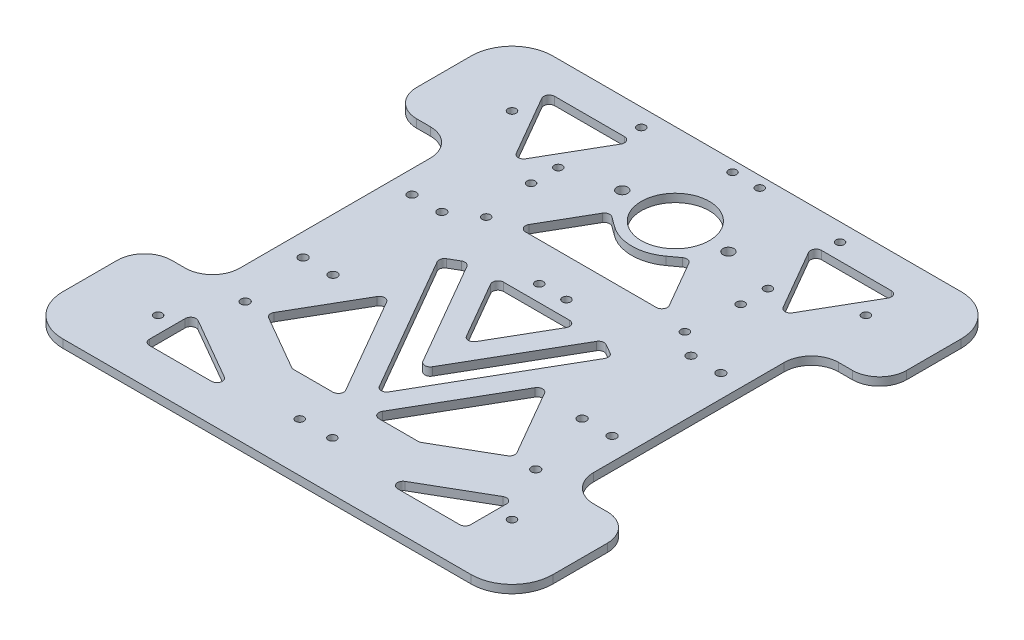
SolidWorks part; units mm, degrees
material "ABS"
ref_plane "Спереди" through (0, 0, 0) normal (0, 0, 1) x (1, 0, 0)
ref_plane "Сверху" through (0, 0, 0) normal (0, 1, 0) x (1, 0, 0)
ref_plane "Справа" through (0, 0, 0) normal (1, 0, 0) x (0, 0, -1)
sketch "Sketch1" plane through (0, 0, 0) normal (0, 1, 0) x (1, 0, 0)
  line L1 (-90, 90) -> (90, 90)
  line L2 (-90, 90) -> (-90, -90)
  line L3 (-90, -90) -> (90, -90)
  line L4 (90, 90) -> (90, -90)
  line L5 (-90, 90) -> (90, -90) construction
  line L6 (-90, -90) -> (90, 90) construction
  point P0 (0, 0)
  dimension "D1" = 180
  dimension "D2" = 180
extrude "Boss-Extrude1" add sketch "Sketch1" along normal blind 3
fillet "Fillet1" radius 15 4 edges at (-90, 1.5, -90) (90, 1.5, -90) (-90, 1.5, 90) (90, 1.5, 90)
sketch "Sketch2" plane through (0, 3, 0) normal (0, 1, 0) x (1, 0, 0)
  line L0 (0, 0) -> (-77.5, 0) construction
  line L1 (2.75, 0) -> (-2.75, 0) construction
  line L2 (-90, 75) -> (-90, -75) construction
  line L3 (-90, 45) -> (-65, 45)
  line L4 (-90, 45) -> (-90, -45)
  line L5 (-90, -45) -> (-65, -45)
  line L6 (-65, 45) -> (-65, -45)
  line L7 (-90, 45) -> (-65, -45) construction
  line L8 (-90, -45) -> (-65, 45) construction
  line L9 (0, 0) -> (0, 45) construction
  line L10 (90, -45) -> (65, 45) construction
  line L11 (90, 45) -> (65, -45) construction
  line L12 (65, 45) -> (65, -45)
  line L13 (90, -45) -> (65, -45)
  line L14 (90, 45) -> (90, -45)
  line L15 (90, 45) -> (65, 45)
  circle A0 centre (-56.75, 20) radius 1.6
  circle A1 centre (-45.75, 20) radius 1.6
  circle A2 centre (-56.75, -20) radius 1.6
  circle A3 centre (-45.75, -20) radius 1.6
  circle A4 centre (45.75, 20) radius 1.6
  circle A5 centre (56.75, 20) radius 1.6
  circle A6 centre (45.75, -20) radius 1.6
  circle A7 centre (56.75, -20) radius 1.6
  dimension "D1" = 25
  dimension "D2" = 90
extrude "Cut-Extrude2" cut sketch "Sketch2" against normal through all
fillet "Fillet2" radius 10 8 edges at (-65, 1.5, 45) (-65, 1.5, -45) (65, 1.5, -45) (65, 1.5, 45) (90, 1.5, -45) (90, 1.5, 45) (-90, 1.5, 45) (-90, 1.5, -45)
hole_wizard "Диаметр отверстия Ø3.0 (3)1" positions "Эскиз2" profile "Эскиз1" hole size "Ø3.0" standard "Ansi Metric" end condition up to next
sketch "Эскиз2" plane through (0, 3, 0) normal (0, 1, 0) x (1, 0, 0)
  line L7 (-65, -65) -> (-65, 65) construction
  line L9 (65, 65) -> (65, -65) construction
  line L11 (-90, 65) -> (-65, 65) construction
  line L12 (-90, 75) -> (-90, 55) construction
  line L13 (-65, 65) -> (65, 65) construction
  line L14 (65, 65) -> (90, 65) construction
  line L15 (90, 55) -> (90, 75) construction
  line L17 (90, -65) -> (65, -65) construction
  line L18 (90, -75) -> (90, -55) construction
  line L19 (65, -65) -> (-65, -65) construction
  line L20 (-65, -65) -> (-90, -65) construction
  line L21 (-90, -55) -> (-90, -75) construction
  line L22 (-65, 65) -> (-65, 90) construction
  line L23 (75, 90) -> (-75, 90) construction
  point P15 (-65, -65)
  point P16 (-65, 65)
  point P19 (65, 65)
  point P20 (65, -65)
sketch "Эскиз1" plane through (-65, 3, 65) normal (1, 0, 0) x (0, 0, 1)
  line L0 (0, 0) -> (0, 3)
  line L1 (0, 3) -> (1.5, 3)
  line L2 (1.5, 3) -> (1.5, 0)
  line L5 (1.5, 0) -> (0, 0)
  line L11 (0, -6.35) -> (0, 107.95) construction
  dimension "Диаметр сквозного отверстия" = 3
  dimension "Глубина сквозного отверстия" = 3
hole_wizard "Диаметр отверстия Ø3.0 (3)2" positions "Эскиз4" profile "Эскиз3" hole size "Ø3.0" standard "Ansi Metric" end condition up to next
sketch "Эскиз4" plane through (0, 3, 0) normal (0, 1, 0) x (1, 0, 0)
  line L0 (90, 65) -> (38.5, 65) construction
  line L1 (90, 55) -> (90, 75) construction
  line L2 (38.5, 65) -> (-38.5, 65) construction
  line L3 (-38.5, 65) -> (-90, 65) construction
  line L4 (-90, 75) -> (-90, 55) construction
  line L12 (-38.5, 15) -> (-5, 15) construction
  line L13 (-5, 15) -> (5, 15) construction
  line L14 (5, 15) -> (38.5, 15) construction
  line L16 (38.5, 86) -> (5, 86) construction
  line L17 (5, 86) -> (-5, 86) construction
  line L18 (-5, 86) -> (-38.5, 86) construction
  line L20 (38.5, 15) -> (38.5, 45.5) construction
  line L21 (38.5, 45.5) -> (38.5, 55.5) construction
  line L22 (38.5, 55.5) -> (38.5, 86) construction
  line L24 (-38.5, 86) -> (-38.5, 55.5) construction
  line L25 (-38.5, 55.5) -> (-38.5, 45.5) construction
  line L26 (-38.5, 45.5) -> (-38.5, 15) construction
  line L28 (75, 90) -> (-75, 90) construction
  point P63 (-5, 15)
  point P66 (-38.5, 45.5)
  point P69 (-38.5, 55.5)
  point P72 (5, 15)
  point P75 (38.5, 45.5)
  point P78 (38.5, 55.5)
  point P81 (5, 86)
  point P84 (-5, 86)
  dimension "D1" = 10
  dimension "D2" = 71
  dimension "D3" = 77
  dimension "D4" = 4
sketch "Эскиз3" plane through (-5, 3, -15) normal (1, 0, 0) x (0, 0, 1)
  line L0 (0, 0) -> (0, 3)
  line L1 (0, 3) -> (1.5, 3)
  line L2 (1.5, 3) -> (1.5, 0)
  line L5 (1.5, 0) -> (0, 0)
  line L11 (0, -6.35) -> (0, 107.95) construction
  dimension "Диаметр сквозного отверстия" = 3
  dimension "Глубина сквозного отверстия" = 3
hole_wizard "Диаметр отверстия Ø4.0 (4)1" positions "Эскиз6" profile "Эскиз5" hole size "Ø4.0" standard "Ansi Metric" end condition up to next
sketch "Эскиз6" plane through (0, 3, 0) normal (0, 1, 0) x (1, 0, 0)
  line L0 (0, 90) -> (0, 60) construction
  line L1 (75, 90) -> (-75, 90) construction
  line L2 (0, 60) -> (0, -90) construction
  line L3 (-75, -90) -> (75, -90) construction
  line L5 (-19.5, 60) -> (19.5, 60) construction
  point P1 (-19.5, 60)
  point P20 (19.5, 60)
  dimension "D1" = 39
  dimension "D2" = 30
sketch "Эскиз5" plane through (-19.5, 3, -60) normal (1, 0, 0) x (0, 0, 1)
  line L0 (0, 0) -> (0, 3)
  line L1 (0, 3) -> (2, 3)
  line L2 (2, 3) -> (2, 0)
  line L5 (2, 0) -> (0, 0)
  line L11 (0, -6.35) -> (0, 107.95) construction
  dimension "Диаметр сквозного отверстия" = 4
  dimension "Глубина сквозного отверстия" = 3
sketch "Sketch3" plane through (0, 3, 0) normal (0, 1, 0) x (1, 0, 0)
  line L0 (0, -90) -> (0, -72) construction
  line L1 (-75, -90) -> (75, -90) construction
  line L2 (0, -72) -> (-6, -72) construction
  circle A0 centre (-6, -72) radius 1.5
  circle A1 centre (6, -72) radius 1.5
  circle A2 centre (53.3716, -44.65) radius 1.6
  circle A3 centre (-53.3716, -44.65) radius 1.6
  arc A4 (-52.7899, -46.1405) -> (-54.9533, -44.8915) centre (-53.3716, -44.65) ccw construction
  arc A5 (54.9533, -44.8915) -> (52.7899, -46.1405) centre (53.3716, -44.65) ccw construction
  dimension "D2" = 3
  dimension "D1" = 18
  dimension "D3" = 12
extrude "Cut-Extrude3" cut sketch "Sketch3" against normal through all
sketch "Sketch4" plane through (0, 3, 0) normal (0, 1, 0) x (1, 0, 0)
  circle A0 centre (-36, 83.5) radius 1.5
  circle A1 centre (37, 83.5) radius 1.5
  circle A2 centre (37, 26.5) radius 1.5
  circle A3 centre (-36, 26.5) radius 1.5
  circle A4 centre (-36, 26.5) radius 1.5 construction
  circle A5 centre (37, 26.5) radius 1.5 construction
  circle A7 centre (37, 83.5) radius 1.5 construction
  circle A8 centre (-36, 83.5) radius 1.5 construction
extrude "Cut-Extrude4" cut sketch "Sketch4" against normal through all
sketch "Sketch5" plane through (0, 3, 0) normal (0, 1, 0) x (1, 0, 0)
  line L0 (0, 0) -> (0, -90) construction
  line L1 (-75, -90) -> (75, -90) construction
  line L2 (31.7543, 5) -> (0, -50)
  line L3 (0, -18) -> (15.5885, 9)
  line L4 (15.5885, 9) -> (-15.5885, 9)
  line L5 (-15.5885, 9) -> (0, -18)
  line L6 (31.7543, 5) -> (24.8261, 9)
  line L7 (6.9282, -38) -> (0, -34) construction
  line L8 (24.8261, 9) -> (0, -34)
  line L9 (31.7543, 5) -> (0, -34) construction
  line L10 (6.9282, -38) -> (24.8261, 9) construction
  line L11 (15.5885, 9) -> (24.8261, 9) construction
  line L12 (-31.7543, 5) -> (0, -50)
  line L13 (-24.8261, 9) -> (0, -34)
  line L14 (-31.7543, 5) -> (-24.8261, 9)
  line L15 (-5, -57.3397) -> (-23.3923, -57.3397)
  line L16 (-29, -15.7705) -> (-5, -57.3397)
  line L17 (29, -15.7705) -> (5, -57.3397)
  line L18 (5, -57.3397) -> (23.3923, -57.3397)
  line L19 (45.5981, -44.5192) -> (29, -15.7705)
  line L20 (-45.5981, -44.5192) -> (-29, -15.7705)
  line L21 (0, 0) -> (0, 44.8771) construction
  line L22 (-14.8005, 50.9961) -> (-27.5, 29)
  line L23 (-59, -57.5662) -> (-26.7254, -76.2)
  line L24 (-27.5, 29) -> (27.5, 29)
  line L25 (27.5, 29) -> (14.8005, 50.9961)
  line L26 (-26.7254, -76.2) -> (-59, -76.2)
  line L27 (-14.8005, 50.9961) -> (-9.4359, 47.0786)
  line L28 (-9.4359, 47.0786) -> (-22.1538, 56.3658) construction
  line L29 (9.4359, 47.0786) -> (14.8005, 50.9961)
  line L30 (-45.5981, -44.5192) -> (-23.3923, -57.3397)
  line L31 (-0.839, -70.3609) -> (-54.5326, -39.3609) construction
  line L32 (45.5981, -44.5192) -> (23.3923, -57.3397)
  line L33 (54.5326, -39.3609) -> (0.839, -70.3609) construction
  line L34 (23.3923, -57.3397) -> (53, -57.3397) construction
  line L35 (45.5981, -44.5192) -> (53, -57.3397) construction
  line L37 (-49.0076, 49.3003) -> (-32.7265, 77.5)
  line L38 (-32.7265, 77.5) -> (-65.2887, 77.5)
  line L39 (-65.2887, 77.5) -> (-49.0076, 49.3003)
  line L40 (32.7265, 77.5) -> (65.2887, 77.5)
  line L41 (65.2887, 77.5) -> (49.0076, 49.3003)
  line L42 (49.0076, 49.3003) -> (32.7265, 77.5)
  line L43 (0, 76.6314) -> (-0.367, 75.9958) [skipped]
  line L44 (-59, -76.2) -> (-59, -57.5662)
  line L45 (-61.0326, -50.6192) -> (-7.339, -81.6192) construction
  line L46 (-22.85, -78.2) -> (-32.5, -78.2) construction
  line L47 (59, -57.5662) -> (26.7254, -76.2)
  line L48 (59, -76.2) -> (59, -57.5662)
  line L49 (26.7254, -76.2) -> (59, -76.2)
  circle A0 centre (0, 0) radius 9 construction
  circle A1 centre (-5, 15) radius 1.5 construction
  circle A2 centre (29, -43.4833) radius 13.8564 construction
  circle A3 centre (0, 44.8771) radius 15.8771 construction
  circle A4 centre (-49.0076, 68.1001) radius 9.3999 construction
  circle A5 centre (-38.5, 55.5) radius 1.5 construction
  circle A6 centre (0, 60) radius 12.5
  arc A7 (-9.4359, 47.0786) -> (9.4359, 47.0786) centre (0, 60) ccw
  circle A8 centre (-36, 83.5) radius 1.5 construction
  circle A9 centre (0, 60) radius 14 construction
  point P12 (15.8771, -14.5)
  point P51 (23.3923, -57.3397)
  dimension "D12" = 1.5
  dimension "D1" = 6
  dimension "D2" = 8
  dimension "D3" = 8
  dimension "D4" = 8
  dimension "D5" = 5
  dimension "D6" = 48
  dimension "D7" = 20
  dimension "D8" = 55
  dimension "D9" = 6
  dimension "D10" = 6
  dimension "D11" = 6
  dimension "D13" = 6
  dimension "D14" = 5
  dimension "D15" = 2
extrude "Cut-Extrude5" cut sketch "Sketch5" against normal through all
fillet "Fillet3" radius 2 33 edges at (-5, 1.5, 57.3397) (-23.3923, 1.5, 57.3397) (-45.5981, 1.5, 44.5192) (-29, 1.5, 15.7705) (45.5981, 1.5, 44.5192) (29, 1.5, 15.7705) (23.3923, 1.5, 57.3397) (5, 1.5, 57.3397) (0, 1.5, 34) (0, 1.5, 50) (-31.7543, 1.5, -5) (-24.8261, 1.5, -9) (31.7543, 1.5, -5) (24.8261, 1.5, -9) (0, 1.5, 18) (15.5885, 1.5, -9) (-15.5885, 1.5, -9) (-27.5, 1.5, -29) (27.5, 1.5, -29) (14.8005, 1.5, -50.9961) (-14.8005, 1.5, -50.9961) (49.0076, 1.5, -49.3003) (65.2887, 1.5, -77.5) (32.7265, 1.5, -77.5) (-65.2887, 1.5, -77.5) (-49.0076, 1.5, -49.3003) (-32.7265, 1.5, -77.5) (-59, 1.5, 57.5662) (-59, 1.5, 76.2) (-26.7254, 1.5, 76.2) (26.7254, 1.5, 76.2) (59, 1.5, 57.5662) (59, 1.5, 76.2)
